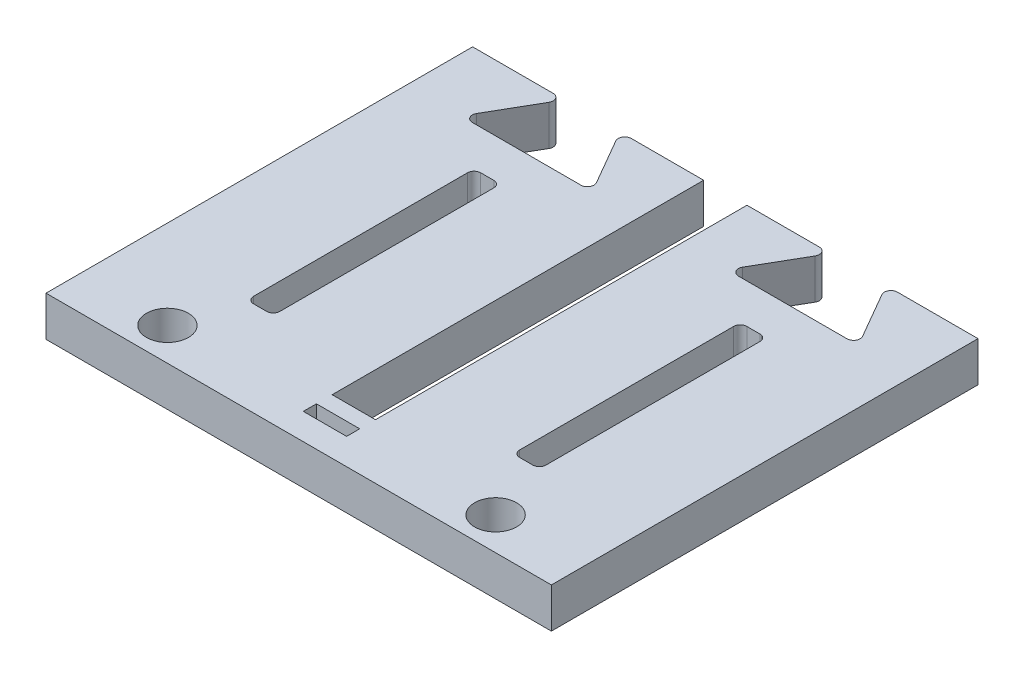
SolidWorks part; units mm, degrees
ref_plane "Front Plane" through (0, 0, 0) normal (0, 0, 1) x (1, 0, 0)
ref_plane "Top Plane" through (0, 0, 0) normal (0, 1, 0) x (1, 0, 0)
ref_plane "Right Plane" through (0, 0, 0) normal (1, 0, 0) x (0, 0, -1)
sketch "Sketch1" plane through (0, 0, 0) normal (0, 1, 0) x (1, 0, 0)
  line L0 (-19.25, 0) -> (-19.25, 32.5)
  line L1 (-19.25, 32.5) -> (-12.25, 32.5)
  line L2 (-12.25, 32.5) -> (-15.1368, 27.5)
  line L3 (-15.1368, 27.5) -> (-5.1368, 27.5)
  line L4 (-5.1368, 27.5) -> (-8.0235, 32.5)
  line L5 (-8.0235, 32.5) -> (8.0235, 32.5)
  line L6 (8.0235, 32.5) -> (5.1368, 27.5)
  line L7 (5.1368, 27.5) -> (15.1368, 27.5)
  line L8 (15.1368, 27.5) -> (12.25, 32.5)
  line L9 (12.25, 32.5) -> (19.25, 32.5)
  line L10 (19.25, 32.5) -> (19.25, 0)
  line L11 (19.25, 0) -> (-19.25, 0)
  point P3 (0, 0)
  dimension "D1" = 32.5
  dimension "D2" = 38.5
  dimension "D3" = 7
  dimension "D4" = 10
  dimension "D5" = 10
  dimension "D6" = 7
  dimension "D7" = 5
  dimension "D11" = 60
  dimension "D12" = 60
  dimension "D13" = 60
extrude "Boss-Extrude1" add sketch "Sketch1" along normal blind 3.05
fillet "Fillet3" radius 0.5 8 edges at (15.1368, 1.525, -27.5) (12.25, 1.525, -32.5) (5.1368, 1.525, -27.5) (8.0235, 1.525, -32.5) (-8.0235, 1.525, -32.5) (-5.1368, 1.525, -27.5) (-15.1368, 1.525, -27.5) (-12.25, 1.525, -32.5)
sketch "Sketch2" plane through (0, 3.05, 0) normal (0, 1, 0) x (1, 0, 0)
  line L0 (0, 0) -> (0, 32.5) construction
  line L3 (1.65, 4.2) -> (-1.65, 4.2)
  line L4 (1.65, 4.2) -> (1.65, 66)
  line L5 (1.65, 66) -> (-1.65, 66)
  line L6 (-1.65, 4.2) -> (-1.65, 66)
  line L7 (-1.65, 3) -> (1.65, 3)
  line L8 (-1.65, 3) -> (-1.65, 2)
  line L9 (-1.65, 2) -> (1.65, 2)
  line L10 (1.65, 3) -> (1.65, 2)
  line L11 (-19.25, 0) -> (19.25, 0) construction
  line L12 (-19.25, 0) -> (-19.25, 72.5) construction
  line L13 (-19.25, 72.5) -> (19.25, 72.5) construction
  line L14 (19.25, 0) -> (19.25, 72.5) construction
  point P8 (0, 4.2)
  point P13 (0, 3)
  dimension "D1" = 3.3
  dimension "D2" = 61.8
  dimension "D3" = 1
  dimension "D4" = 1.2
  dimension "D5" = 72.5
  dimension "D6" = 6.5
extrude "Cut-Extrude1" cut sketch "Sketch2" against normal through all
sketch "Sketch6" plane through (0, 3.05, 0) normal (0, 1, 0) x (1, 0, 0)
  line L0 (0, 0) -> (0, 18.0616) construction
  line L1 (-6.0028, 27.5) -> (-14.2707, 27.5) construction
  line L2 (-11.1368, 24.5) -> (-9.1368, 24.5)
  line L3 (-11.1368, 24.5) -> (-11.1368, 7.2)
  line L4 (-11.1368, 7.2) -> (-9.1368, 7.2)
  line L5 (-9.1368, 24.5) -> (-9.1368, 7.2)
  line L6 (-1.65, 4.2) -> (1.65, 4.2) construction
  line L7 (11.1368, 7.2) -> (9.1368, 7.2)
  line L8 (9.1368, 24.5) -> (9.1368, 7.2)
  line L9 (11.1368, 24.5) -> (9.1368, 24.5)
  line L10 (11.1368, 24.5) -> (11.1368, 7.2)
  point P9 (-10.1368, 27.5)
  point P10 (-10.1368, 24.5)
  dimension "D1" = 2
  dimension "D2" = 3
  dimension "D3" = 3
extrude "Cut-Extrude2" cut sketch "Sketch6" against normal through all
fillet "Fillet4" radius 0.5 8 edges at (9.1368, 1.525, -7.2) (11.1368, 1.525, -7.2) (11.1368, 1.525, -24.5) (9.1368, 1.525, -24.5) (-11.1368, 1.525, -7.2) (-9.1368, 1.525, -7.2) (-9.1368, 1.525, -24.5) (-11.1368, 1.525, -24.5)
sketch "Head Mounting Hole Locations" plane through (0, 3.05, 0) normal (0, 1, 0) x (1, 0, 0)
  line L0 (0, 0) -> (0, 16.3288) construction
  line L1 (-19.25, 0) -> (19.25, 0) construction
  circle A0 centre (-12.5, 2.5) radius 1.5
  circle A1 centre (12.5, 2.5) radius 1.5
  dimension "D1" = 3
  dimension "D2" = 12.5
  dimension "D3" = 2.5
hole_wizard "M3 Clearance Head Mounting Holes" positions "Sketch4" profile "Sketch5" hole size "M3" standard "ANSI Metric" end condition through all
sketch "Sketch4" plane through (0, 3.05, 0) normal (0, 1, 0) x (1, 0, 0)
  point P0 (-12.5, 2.5)
  point P3 (12.5, 2.5)
sketch "Sketch5" plane through (-12.5, 3.05, -2.5) normal (1, 0, 0) x (0, 0, 1)
  line L0 (0, 0) -> (0, 3.05)
  line L1 (0, 3.05) -> (1.6, 3.05)
  line L2 (1.6, 3.05) -> (1.6, 0)
  line L5 (1.6, 0) -> (0, 0)
  line L11 (0, -6.35) -> (0, 107.95) construction
  dimension "Thru Hole Dia." = 3.2
  dimension "Thru Hole Depth" = 3.05
